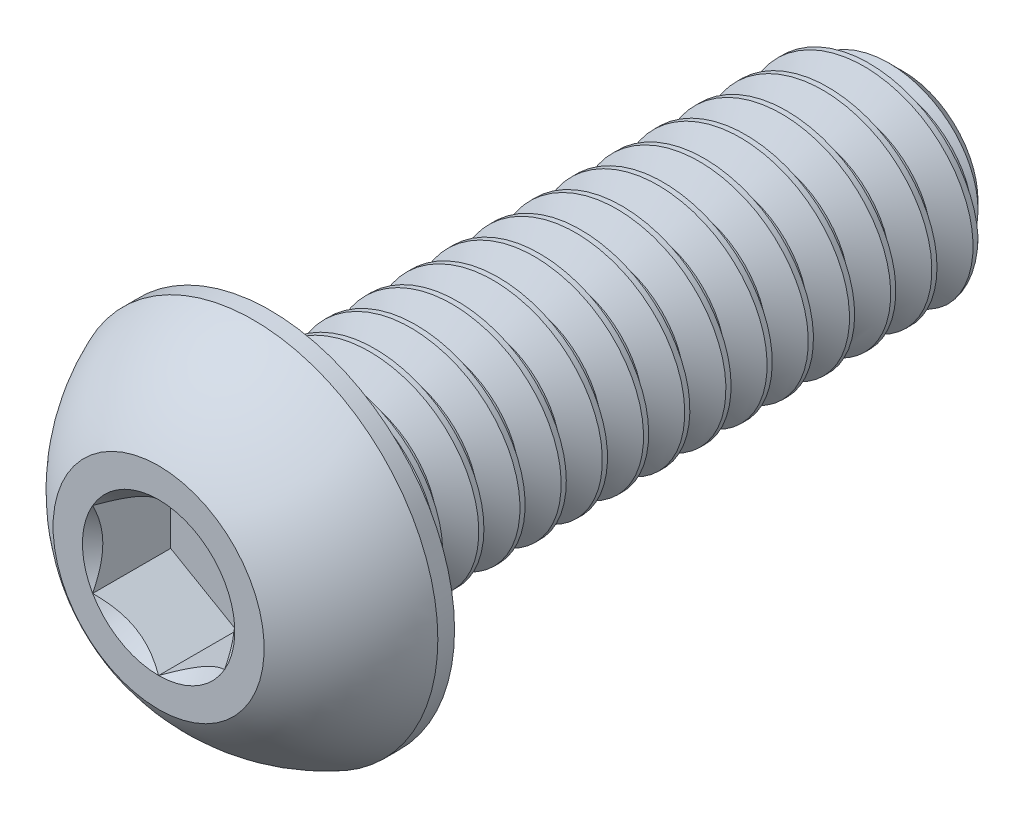
SolidWorks part; units mm, degrees
ref_plane "Front" through (0, 0, 0) normal (0, 0, 1) x (1, 0, 0)
ref_plane "Top" through (0, 0, 0) normal (0, 1, 0) x (1, 0, 0)
ref_plane "Right" through (0, 0, 0) normal (1, 0, 0) x (0, 0, -1)
sketch "Sketch1" plane through (0, 0, 0) normal (1, 0, 0) x (0, 0, -1)
  line L2 (3.3528, 3.175) -> (22.4028, 3.175)
  line L3 (22.4028, 3.175) -> (22.4028, 0)
  line L4 (22.4028, 0) -> (3.3528, 0)
  line L6 (2.8499, 5.5499) -> (3.3528, 5.5499) construction
  line L7 (22.4028, 3.175) -> (22.4028, -3.175) construction
  line L8 (0, 0) -> (3.3528, 0) construction
  line L9 (3.3528, 5.5499) -> (3.3528, -5.5499) construction
  line L11 (3.3528, 3.175) -> (3.3528, 0)
  line L13 (0, 1.9844) -> (0, -1.9844) construction
  line L14 (0, 1.9844) -> (0, 3.175) construction
  arc A3 (0, 3.175) -> (2.8499, 5.5499) centre (5.0603, 0) cw construction
  dimension "D1" = 0.5029
revolve "Revolve1" add sketch "Sketch1" angle 360 mid plane about L4
sketch "Sketch3" plane through (0, 0, -22.4028) normal (0, 0, -1) x (-1, 0, 0)
  circle A0 centre (0, 0) radius 3.175
curve "Helix/Spiral1" pitch 1.239 height 22.4028 radius 3.175 centre (0, 0, -22.4028) axis (0, 0, 1) start towards (0, 1, 0)
sketch "Sketch2" plane through (0, 0, 0) normal (1, 0, 0) x (0, 0, -1)
  line L0 (22.4028, 3.175) -> (23.4869, 3.175)
  line L1 (23.4869, 3.175) -> (23.0223, 2.3702)
  line L2 (23.0223, 2.3702) -> (22.8674, 2.3702)
  line L3 (22.8674, 2.3702) -> (22.4028, 3.175)
  line L4 (22.6351, 2.7726) -> (23.2546, 2.7726) construction
  dimension "D1" = 60
  dimension "D2" = 0.1549
  dimension "D3" = 0.6195
chamfer "Chamfer1" distance 0.9293 angle 45 1 edges at (0, 3.175, -22.4028)
sweep "Cut-Sweep1" cut profiles "Sketch2" path "Helix/Spiral1" align with end faces yes
sketch "Sketch7" plane through (0, 0, 0) normal (1, 0, 0) x (0, 0, -1)
  line L6 (2.8499, 5.5499) -> (3.3528, 5.5499) construction
  line L8 (0, 0) -> (3.3528, 0) construction
  line L11 (3.3528, 5.5499) -> (3.3528, -5.5499) construction
  line L12 (2.8499, 5.5499) -> (3.3528, 5.5499)
  line L13 (0, 0) -> (3.3528, 0)
  line L14 (0, 1.9844) -> (0, -1.9844) construction
  line L15 (3.3528, 5.5499) -> (3.3528, 0)
  line L16 (0, 3.175) -> (0, 0)
  arc A2 (2.8499, 5.5499) -> (0, 3.175) centre (5.0603, 0) ccw construction
  arc A3 (2.8499, 5.5499) -> (0, 3.175) centre (5.0603, 0) ccw
revolve "Revolve2" add sketch "Sketch7" angle 360 mid plane about L13
sketch "Sketch5" plane through (0, 0, 0) normal (0, 0, 1) x (1, 0, 0)
  line L1 (1.9844, -1.1457) -> (1.9844, 1.1457)
  line L2 (1.9844, 1.1457) -> (0, 2.2914)
  line L3 (0, 2.2914) -> (-1.9844, 1.1457)
  line L4 (-1.9844, 1.1457) -> (-1.9844, -1.1457)
  line L5 (-1.9844, -1.1457) -> (0, -2.2914)
  line L6 (0, -2.2914) -> (1.9844, -1.1457)
  circle A0 centre (0, 0) radius 1.9844 construction
extrude "Cut-Extrude2" cut sketch "Sketch5" against normal blind 2.347
sketch "Sketch6" plane through (0, 0, 0) normal (0, 0, 1) x (1, 0, 0)
  circle A0 centre (0, 0) radius 2.2914
extrude "Cut-Extrude3" cut sketch "Sketch6" against normal blind 2.347 draft 45
sketch "Sketch9" [suppressed] plane through (0, 0, -3.3528) normal (0, 0, 1) x (1, 0, 0)
  circle A2 centre (0, 0) radius 3.175
extrude "Boss-Extrude2" [suppressed] add sketch "Sketch9" against normal offset from surface (76.2 mm away) 22.225 up to face at (0, 2.2457, -22.4028)
sketch "Sketch10" plane through (0, 0, 0) normal (1, 0, 0) x (0, 0, -1)
  line L0 (22.4028, 3.175) -> (22.4028, -3.175) construction
  point P0 (20.5443, -3.175)
  dimension "D1" = 1.8585
equation "\"D3@Helix/Spiral1\" = \"Lg@Sketch1\" + \"Head Ht@Sketch1\""
equation "\"D2@Sketch2\" = \"D4@Helix/Spiral1\" * .125"
equation "\"D3@Sketch2\" = \"D4@Helix/Spiral1\" * .5"
equation "\"D1@Chamfer1\" = \"D4@Helix/Spiral1\" * .75"
equation "\"D1@Cut-Extrude2\" = \"Head Ht@Sketch1\" * .7"
equation "\"D1@Sketch1\" = \"Head Ht@Sketch1\" * .15"
equation "\"D1@Sketch10\" = \"D4@Helix/Spiral1\" * 1.5"
equation "\"D1@Cut-Extrude3\" = \"D1@Cut-Extrude2\""
